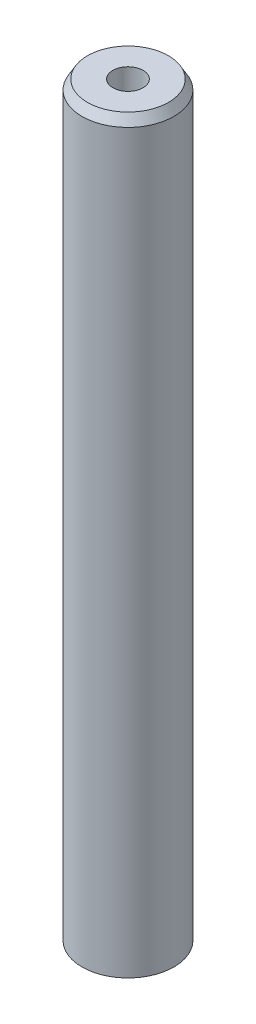
SolidWorks part; units mm, degrees
ref_plane "Front Plane" through (0, 0, 0) normal (0, 0, 1) x (1, 0, 0)
ref_plane "Top Plane" through (0, 0, 0) normal (0, 1, 0) x (1, 0, 0)
ref_plane "Right Plane" through (0, 0, 0) normal (1, 0, 0) x (0, 0, -1)
sketch "Sketch1" plane through (0, 0, 0) normal (0, 1, 0) x (1, 0, 0)
  circle A0 centre (0, 0) radius 22.5
  dimension "SHAFT_OD" = 45
extrude "Boss-Extrude1" add sketch "Sketch1" along normal blind 368.0931
sketch "Sketch2" plane through (0, 0, 0) normal (0, 1, 0) x (1, 0, 0)
  circle A0 centre (0, 0) radius 7.4034
  dimension "BORE_D" = 14.8068
extrude "Cut-Extrude1" cut sketch "Sketch2" along normal through all
chamfer "Chamfer1" distance 4.6215 angle 30 2 edges at (0, 368.0931, 22.5) (0, 0, 22.5) first distance on face at (0, 368.0931, 22.5) first distance on face at (0, 0, 7.4034)
